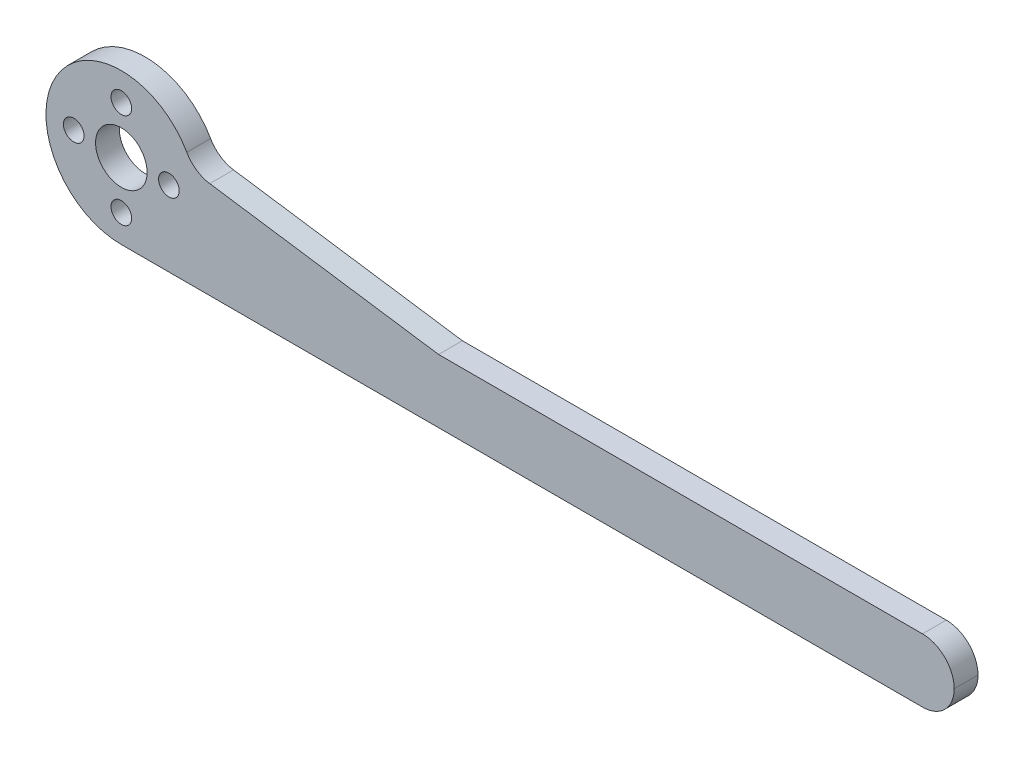
SolidWorks part; units mm, degrees
ref_plane "Front" through (0, 0, 0) normal (0, 0, 1) x (1, 0, 0)
ref_plane "Top" through (0, 0, 0) normal (0, 1, 0) x (1, 0, 0)
ref_plane "Right" through (0, 0, 0) normal (1, 0, 0) x (0, 0, -1)
sketch "Esquisse1" plane through (0, 0, 0) normal (0, 0, 1) x (1, 0, 0)
  line L0 (6, 0) -> (0, 0) construction
  line L1 (0, 0) -> (0, 6) construction
  circle A0 centre (0, 0) radius 9.5
  circle A1 centre (6, 0) radius 1.3
  circle A2 centre (0, 6) radius 1.3
  circle A3 centre (-6, 0) radius 1.3
  circle A4 centre (0, -6) radius 1.3
  circle A5 centre (0, 0) radius 3.25
  dimension "D1" = 2.6
  dimension "D3" = 6.5
  dimension "D4" = 19
  dimension "D2" = 6
extrude "Boss.-Extru.1" add sketch "Esquisse1" along normal blind 3
sketch "Esquisse2" plane through (0, 0, 3) normal (0, 0, 1) x (1, 0, 0)
  line L0 (0, -9.5) -> (40, -9.5)
  line L1 (40, -9.5) -> (40, -1.5)
  line L2 (40, -1.5) -> (9, 3.0414)
  line L3 (9, 3.0414) -> (9, -0.5)
  line L4 (9, -0.5) -> (0, -9.5)
  line L5 (0, -9.5) -> (0, 0) construction
  circle A0 centre (0, 0) radius 9.5 construction
  point P5 (9, -0.8038)
  dimension "D1" = 40
  dimension "D2" = 8
  dimension "D3" = 9
  dimension "D4" = 9
extrude "Boss.-Extru.2" add sketch "Esquisse2" against normal blind 3
sketch "Esquisse3" plane through (0, 0, 3) normal (0, 0, 1) x (1, 0, 0)
  line L0 (40, -9.5) -> (105, -9.5)
  line L1 (105, -9.5) -> (105, -1.5)
  line L2 (105, -1.5) -> (40, -1.5)
  line L3 (40, -1.5) -> (40, -9.5)
  circle A0 centre (0, 0) radius 3.25 construction
  dimension "D1" = 105
extrude "Boss.-Extru.3" add sketch "Esquisse3" against normal blind 3
fillet "Congé1" radius 4 3 edges at (9, 3.0414, 1.5) (105, -9.5, 1.5) (105, -1.5, 1.5)
